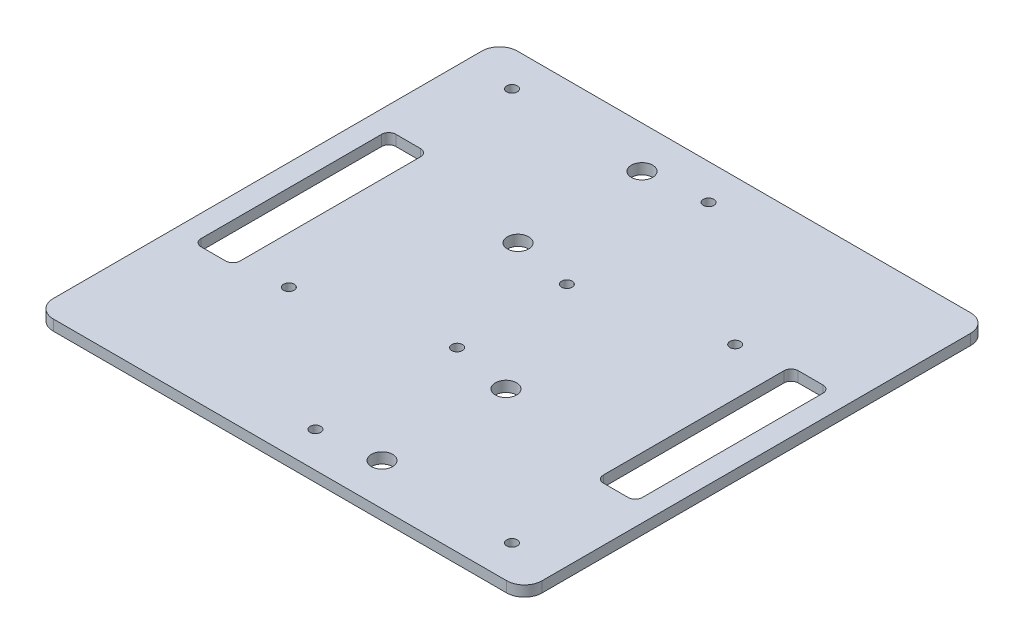
SolidWorks part; units mm, degrees
material "Pine"
ref_plane "Front Plane" through (0, 0, 0) normal (0, 0, 1) x (1, 0, 0)
ref_plane "Top Plane" through (0, 0, 0) normal (0, 1, 0) x (1, 0, 0)
ref_plane "Right Plane" through (0, 0, 0) normal (1, 0, 0) x (0, 0, -1)
sketch "Sketch1" plane through (0, 0, 0) normal (0, 1, 0) x (1, 0, 0)
  line L1 (69, -65.5) -> (-69, -65.5)
  line L2 (69, -65.5) -> (69, 65.5)
  line L3 (69, 65.5) -> (-69, 65.5)
  line L4 (-69, -65.5) -> (-69, 65.5)
  line L5 (69, -65.5) -> (-69, 65.5) construction
  line L6 (69, 65.5) -> (-69, -65.5) construction
  point P0 (0, 0)
  dimension "D1" = 138
  dimension "D2" = 131
extrude "Boss-Extrude1" add sketch "Sketch1" along normal blind 3
sketch "Sketch2" plane through (0, 3, 0) normal (0, 1, 0) x (1, 0, 0)
  line L0 (-11.3319, 36.2) -> (-45.3008, 36.2) construction
  line L1 (69, 65.5) -> (-69, 65.5) construction
  line L3 (-51.8, -27) -> (-62.8, -27)
  line L4 (-69, 65.5) -> (-69, -65.5) construction
  line L5 (-51.8, -27) -> (-51.8, 28)
  line L7 (-51.8, 28) -> (-62.8, 28)
  line L8 (-62.8, -27) -> (-62.8, 28)
  circle A0 centre (-17, 18.7) radius 3
  circle A1 centre (-17, 53.7) radius 3
  circle A2 centre (0, 55.5) radius 1.5
  circle A3 centre (0, 15.5) radius 1.5
  circle A11 centre (-55.5, 55.5) radius 1.5
  circle A13 centre (-38.5, -24.5) radius 1.5
  dimension "D2" = 6
  dimension "D3" = 3
  dimension "D4" = 6
  dimension "D15" = 55
  dimension "D16" = 6.2
  dimension "D17" = 11
  dimension "D18" = 69
  dimension "D21" = 3
  dimension "D27" = 3
  dimension "D5" = 40
  dimension "D6" = 35
  dimension "D7" = 17.5
  dimension "D8" = 29.3
  dimension "D9" = 13.5
  dimension "D10" = 10
  dimension "D11" = 17
  dimension "D12" = 90
  dimension "D13" = 17
  dimension "D14" = 37.5
extrude "Cut-Extrude1" cut sketch "Sketch2" against normal through all
fillet "Fillet1" radius 5 4 edges at (-69, 1.5, -65.5) (69, 1.5, -65.5) (69, 1.5, 65.5) (-69, 1.5, 65.5)
ref_axis "Axis1" through (0, -0.15, 0) along (0, 1, 0)
fillet "Fillet2" radius 2 4 edges at (-62.8, 1.5, -28) (-51.8, 1.5, -28) (-51.8, 1.5, 27) (-62.8, 1.5, 27)
pattern_circular "CirPattern1" count 2 every 180 about axis through (0, -0.15, 0) along (0, 1, 0) of "Cut-Extrude1", "Fillet2"
